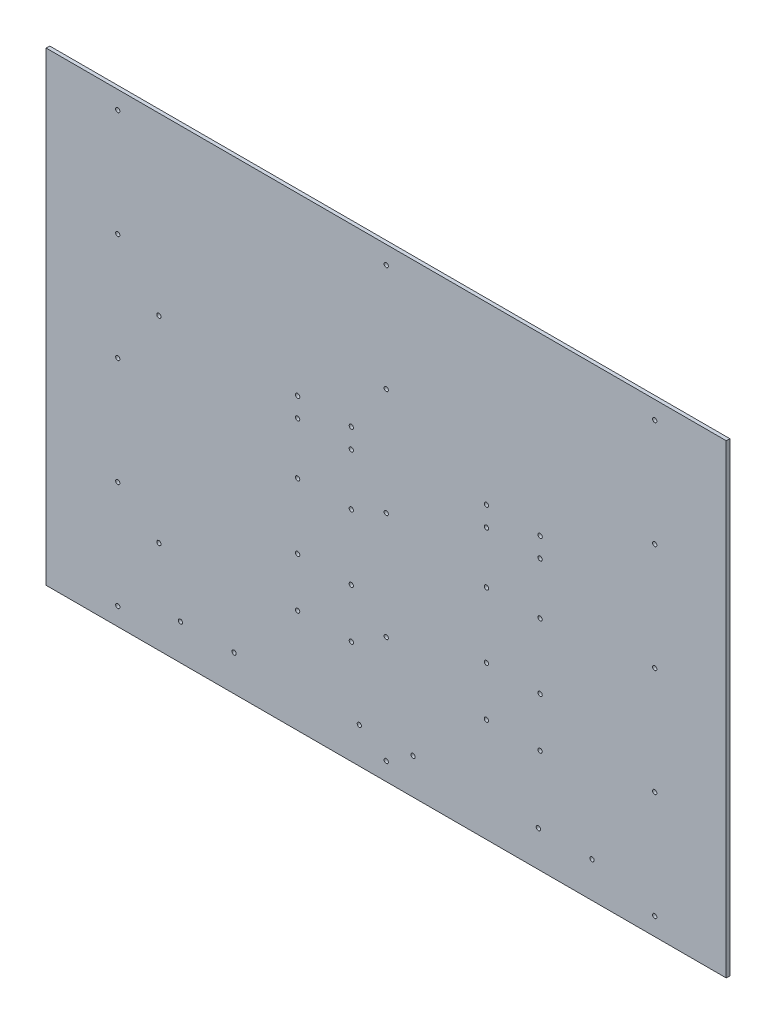
SolidWorks part; units mm, degrees
ref_plane "Płaszczyzna przednia" through (0, 0, 0) normal (0, 0, 1) x (1, 0, 0)
ref_plane "Płaszczyzna górna" through (0, 0, 0) normal (0, 1, 0) x (1, 0, 0)
ref_plane "Płaszczyzna prawa" through (0, 0, 0) normal (1, 0, 0) x (0, 0, -1)
sketch "Szkic1" plane through (0, 0, 0) normal (0, 0, 1) x (1, 0, 0)
  line L1 (-950, -650) -> (950, -650)
  line L2 (-950, -650) -> (-950, 650)
  line L3 (-950, 650) -> (950, 650)
  line L4 (950, -650) -> (950, 650)
  line L5 (-950, -650) -> (950, 650) construction
  line L6 (-950, 650) -> (950, -650) construction
  point P0 (0, 0)
  dimension "D1" = 1900
  dimension "D2" = 1300
extrude "Dodanie-wyciągnięcie1" add sketch "Szkic1" along normal blind 10
hole_wizard "Otwór pod śrubę M101" positions "Szkic2" profile "Szkic3" hole size "M10" standard "Ansi Metric" end condition through all
sketch "Szkic2" plane through (0, 0, 10) normal (0, 0, 1) x (1, 0, 0)
  line L0 (-950, 650) -> (-950, -650) construction
  line L2 (-950, -650) -> (950, -650) construction
  point P0 (-750, -600)
  dimension "D1" = 200
  dimension "D2" = 50
sketch "Szkic3" plane through (-750, -600, 10) normal (1, 0, 0) x (0, -1, 0)
  line L0 (0, 0) -> (0, 10)
  line L1 (0, 10) -> (6, 10)
  line L2 (6, 10) -> (6, 0)
  line L5 (6, 0) -> (0, 0)
  line L11 (0, -6.35) -> (0, 107.95) construction
  dimension "Średnica otworu na wylot" = 12
  dimension "Głębokość otworu na wylot" = 10
pattern_linear "Szyk liniowy1" count 5 spacing 300 along (0, 1, 0) count 3 spacing 750 along (1, 0, 0) of "Otwór pod śrubę M101"
hole_wizard "Otwór pod śrubę M103" positions "Szkic6" profile "Szkic7" hole size "M10" standard "Ansi Metric" end condition through all
sketch "Szkic6" plane through (0, 0, 10) normal (0, 0, 1) x (1, 0, 0)
  line L0 (-950, -650) -> (950, -650) construction
  circle A0 centre (0, -600) radius 6 construction
  point P0 (-75, -550)
  point P2 (75, -550)
  dimension "D1" = 100
  dimension "D2" = 100
  dimension "D3" = 150
  dimension "D4" = 75
sketch "Szkic7" plane through (-75, -550, 10) normal (1, 0, 0) x (0, -1, 0)
  line L0 (0, 0) -> (0, 10)
  line L1 (0, 10) -> (6, 10)
  line L2 (6, 10) -> (6, 0)
  line L5 (6, 0) -> (0, 0)
  line L11 (0, -6.35) -> (0, 107.95) construction
  dimension "Średnica otworu na wylot" = 12
  dimension "Głębokość otworu na wylot" = 10
hole_wizard "Otwór pod śrubę M104" positions "Szkic8" profile "Szkic9" hole size "M10" standard "Ansi Metric" end condition through all
sketch "Szkic8" plane through (0, 0, 10) normal (0, 0, 1) x (1, 0, 0)
  line L0 (-950, -650) -> (950, -650) construction
  circle A0 centre (0, -600) radius 6 construction
  point P0 (-575, -550)
  point P2 (-425, -550)
  point P4 (425, -550)
  point P6 (575, -550)
  dimension "D7" = 575
  dimension "D8" = 575
  dimension "D1" = 100
  dimension "D2" = 100
  dimension "D3" = 100
  dimension "D4" = 100
  dimension "D5" = 150
  dimension "D6" = 150
sketch "Szkic9" plane through (-575, -550, 10) normal (1, 0, 0) x (0, -1, 0)
  line L0 (0, 0) -> (0, 10)
  line L1 (0, 10) -> (6, 10)
  line L2 (6, 10) -> (6, 0)
  line L5 (6, 0) -> (0, 0)
  line L11 (0, -6.35) -> (0, 107.95) construction
  dimension "Średnica otworu na wylot" = 12
  dimension "Głębokość otworu na wylot" = 10
hole_wizard "Otwór pod śrubę M105" positions "Szkic10" profile "Szkic11" hole size "M10" standard "Ansi Metric" end condition through all
sketch "Szkic10" plane through (0, 0, 10) normal (0, 0, 1) x (1, 0, 0)
  point P0 (-635, -390)
  point P3 (-635, 160)
sketch "Szkic11" plane through (-635, -390, 10) normal (1, 0, 0) x (0, -1, 0)
  line L0 (0, 0) -> (0, 10)
  line L1 (0, 10) -> (6, 10)
  line L2 (6, 10) -> (6, 0)
  line L5 (6, 0) -> (0, 0)
  line L11 (0, -6.35) -> (0, 107.95) construction
  dimension "Średnica otworu na wylot" = 12
  dimension "Głębokość otworu na wylot" = 10
hole_wizard "Otwór pod śrubę M106" positions "Szkic12" profile "Szkic13" hole size "M10" standard "Ansi Metric" end condition through all
sketch "Szkic12" plane through (0, 0, 10) normal (0, 0, 1) x (1, 0, 0)
  point P0 (-247.5, -360)
  point P3 (-97.5, -360)
  point P6 (-97.5, -222.5)
  point P9 (-247.5, -222.5)
  point P12 (-97.5, -40)
  point P15 (-247.5, -40)
  point P18 (-247.5, 105)
  point P21 (-97.5, 105)
  point P24 (-97.5, 160)
  point P27 (-247.5, 160)
  point P30 (280, 160)
  point P33 (430, 160)
  point P36 (430, 105)
  point P39 (280, 105)
  point P42 (280, -40)
  point P45 (430, -40)
  point P48 (280, -222.5)
  point P51 (430, -222.5)
  point P54 (430, -360)
  point P57 (280, -360)
sketch "Szkic13" plane through (-247.5, -360, 10) normal (1, 0, 0) x (0, -1, 0)
  line L0 (0, 0) -> (0, 10)
  line L1 (0, 10) -> (6, 10)
  line L2 (6, 10) -> (6, 0)
  line L5 (6, 0) -> (0, 0)
  line L11 (0, -6.35) -> (0, 107.95) construction
  dimension "Średnica otworu na wylot" = 12
  dimension "Głębokość otworu na wylot" = 10
